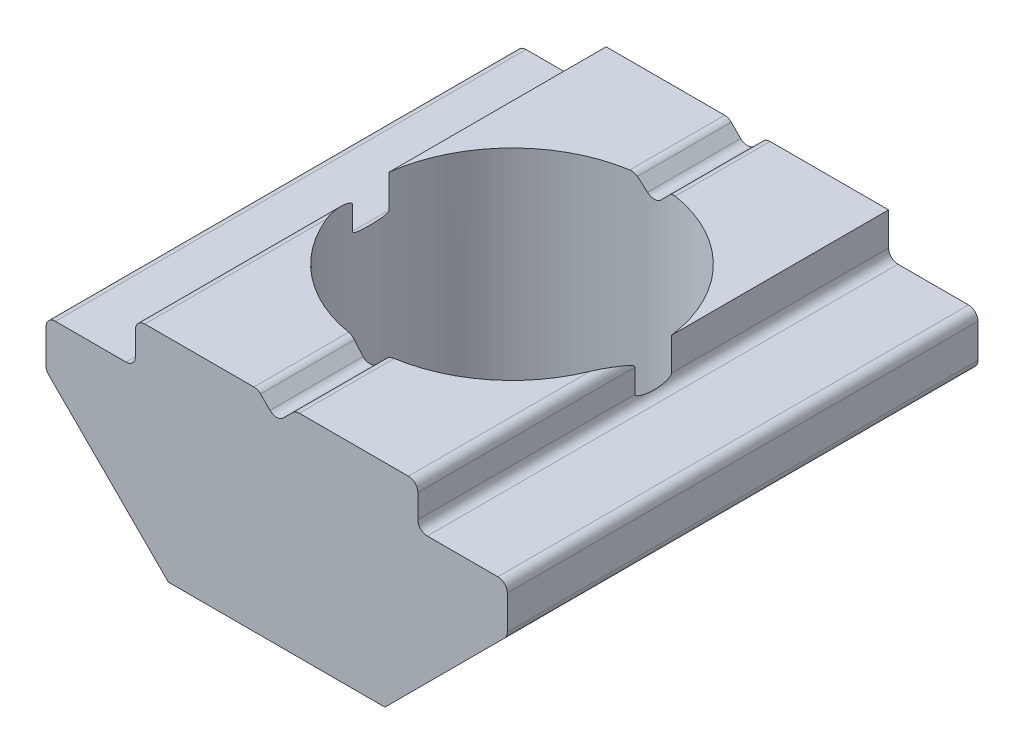
SolidWorks part; units mm, degrees
ref_plane "Front Plane" through (0, 0, 0) normal (0, 0, 1) x (1, 0, 0)
ref_plane "Top Plane" through (0, 0, 0) normal (0, 1, 0) x (1, 0, 0)
ref_plane "Right Plane" through (0, 0, 0) normal (1, 0, 0) x (0, 0, -1)
ref_plane "Plane1" through (0, 0, 5) normal (0, 0, 1) x (1, 0, 0)
sketch "Sketch1" plane through (0, 0, 5) normal (0, 0, 1) x (1, 0, 0)
  line L0 (4.9, -1) -> (4.9, 0.9)
  line L1 (4.9, 0.9) -> (-4.9, 0.9)
  line L2 (-4.9, 0.9) -> (-4.9, -1)
  line L3 (-4.9, -1) -> (-2.3, -3.6)
  line L4 (-2.3, -3.6) -> (2.3, -3.6)
  line L5 (2.3, -3.6) -> (4.9, -1)
extrude "Extrude Body" add sketch "Sketch1" against normal blind 10
sketch "Sketch2" plane through (0, 0, -5) normal (0, 0, -1) x (-1, 0, 0)
  line L0 (4.9, 0.9) -> (3, 0.9)
  line L1 (3, 0.9) -> (3, 0)
  line L2 (3, 0) -> (4.9, 0)
  line L3 (4.9, 0) -> (4.9, 0.9)
extrude "Cut-Extrude1" cut sketch "Sketch2" against normal through all
sketch "Sketch3" plane through (0, 0, -5) normal (0, 0, -1) x (-1, 0, 0)
  line L0 (-4.9, 0) -> (-3, 0)
  line L1 (-3, 0) -> (-3, 0.9)
  line L2 (-3, 0.9) -> (-4.9, 0.9)
  line L3 (-4.9, 0.9) -> (-4.9, 0)
extrude "Cut-Extrude2" cut sketch "Sketch3" against normal through all
sketch "Sketch4" plane through (0, 0, -5) normal (0, 0, -1) x (-1, 0, 0)
  line L0 (0.4, 0.9) -> (-0.4, 0.9)
  line L1 (-0.4, 0.9) -> (0, 0.5)
  line L2 (0, 0.5) -> (0.4, 0.9)
extrude "Cut-Extrude3" cut sketch "Sketch4" against normal through all
hole_wizard "Hole Revolve" positions "Hole Locating Sketch" profile "Hole Cut Out Sketch" hole size "Ø4.2" standard "ANSI Metric" end condition through all
sketch "Hole Locating Sketch" plane through (0, -3.6, 0) normal (0, -1, 0) x (-1, 0, 0)
  point P0 (0, 0)
sketch "Hole Cut Out Sketch" plane through (0, -3.6, 0) normal (1, 0, 0) x (0, 0, -1)
  line L0 (0, 0) -> (0, 4.5)
  line L1 (0, 4.5) -> (3.025, 4.5)
  line L2 (3.025, 4.5) -> (3.025, 0)
  line L5 (3.025, 0) -> (0, 0)
  line L11 (0, -6.35) -> (0, 107.95) construction
  dimension "Thru Hole Dia." = 6.05
  dimension "Thru Hole Depth" = 4.5
fillet "Edge Fillets" radius 0.2 18 edges at (4.9, 0, 0) (3, 0, -2.6941) (3, 0, 2.6941) (-4.9, -1, 0) (3, 0.9, 2.6941) (-3, 0, 2.6941) (-3, 0, -2.6941) (0.4, 0.9, -3.9992) (0, 0.5, 4.0125) (-0.4, 0.9, -3.9992) (4.9, -1, 0) (-3, 0.9, 2.6941) (0, 0.5, -4.0125) (-0.4, 0.9, 3.9992) (-4.9, 0, 0) (-2.3, -3.6, -3.4824) (0.4, 0.9, 3.9992) (2.3, -3.6, -3.4824)
